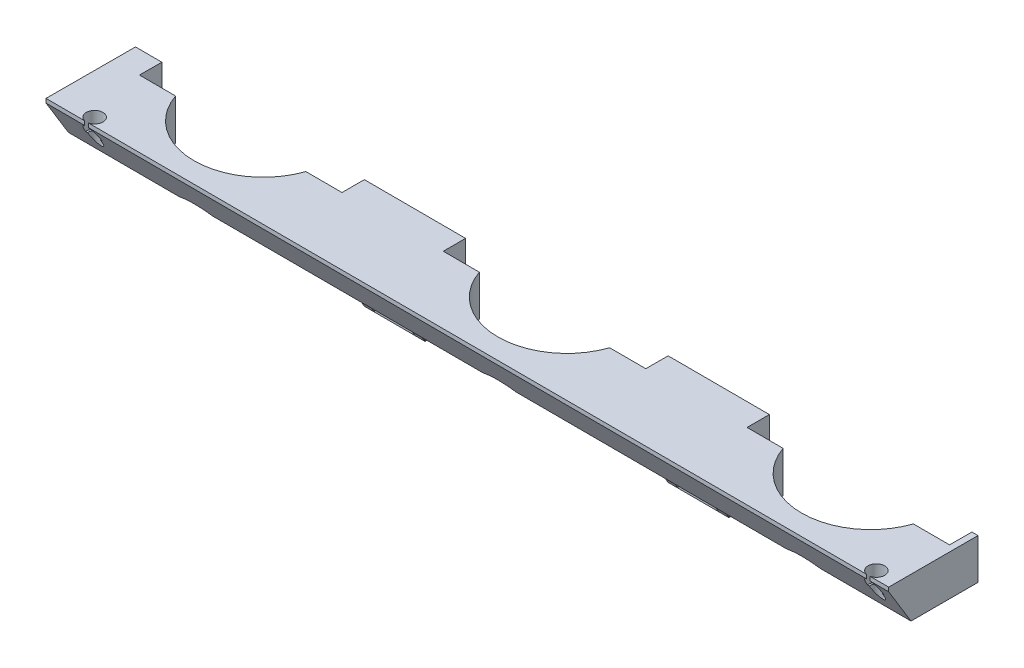
SolidWorks part; units mm, degrees
ref_plane "Płaszczyzna przednia" through (0, 0, 0) normal (0, 0, 1) x (1, 0, 0)
ref_plane "Płaszczyzna górna" through (0, 0, 0) normal (0, 1, 0) x (1, 0, 0)
ref_plane "Płaszczyzna prawa" through (0, 0, 0) normal (1, 0, 0) x (0, 0, -1)
sketch "Sketch2" plane through (0, 0, 0) normal (0, 1, 0) x (1, 0, 0)
  line L2 (-138.973, 39.1792) -> (-139.0228, 17.1793)
  line L3 (-139.0228, 17.1793) -> (73.9767, 16.6977)
  line L4 (74.027, 38.6976) -> (73.9767, 16.6977)
  line L5 (-107.4205, 62.3676) -> (-107.5199, 18.3936) construction
  line L7 (-132.4855, 33.6645) -> (-123.5712, 33.6443)
  line L9 (-132.4855, 33.6645) -> (-132.473, 39.1645)
  line L10 (-82.473, 39.0515) -> (-82.4855, 33.5515)
  line L11 (-138.973, 39.1792) -> (-132.473, 39.1645)
  line L12 (-57.4857, 33.4949) -> (-57.4732, 38.995)
  line L13 (-82.473, 39.0515) -> (-57.4732, 38.995)
  line L14 (-82.4855, 33.5515) -> (-91.3999, 33.5716)
  line L15 (-57.4857, 33.4949) -> (-48.5714, 33.4748)
  line L16 (-7.4857, 33.3819) -> (-16.4001, 33.402)
  line L17 (-7.4732, 38.8819) -> (-7.4857, 33.3819)
  line L18 (17.5141, 33.3253) -> (17.5266, 38.8254)
  line L19 (17.5141, 33.3253) -> (26.4284, 33.3052)
  line L20 (67.5141, 33.2123) -> (58.5997, 33.2325)
  line L21 (67.5266, 38.7123) -> (67.5141, 33.2123)
  line L22 (-7.4732, 38.8819) -> (17.5266, 38.8254)
  line L23 (67.5266, 38.7123) -> (74.027, 38.6976)
  arc A4 (-123.5712, 33.6443) -> (-91.3999, 33.5716) centre (-107.4731, 39.108) ccw
  arc A5 (-48.5714, 33.4748) -> (-16.4001, 33.402) centre (-32.4733, 38.9384) ccw
  arc A6 (26.4284, 33.3052) -> (58.5997, 33.2325) centre (42.5265, 38.7688) ccw
  point P4 (-104.1372, 39.0751)
  point P8 (-115.6371, 39.1103)
  point P12 (-95.973, 39.082)
  point P15 (-107.4702, 40.3806)
  dimension "D3" = 31.5
  dimension "D5" = 213
  dimension "D9" = 6.5
  dimension "D4" = 50.0001
  dimension "D14" = 34
  dimension "D11" = 17
  dimension "D1" = 213
  dimension "D2" = 22
  dimension "D6" = 360
  dimension "D7" = 13.5
  dimension "D8" = 213.0005
  dimension "D10" = 0
  dimension "D12" = 5.5
  dimension "D13" = 50
  dimension "D15" = 3
  dimension "D16" = 89.999
  dimension "D17" = 8.9143
extrude "Boss-Extrude3" add sketch "Sketch2" along normal blind 10
sketch "Sketch4" plane through (0.0879, 0, -38.8648) normal (0.0023, 0, -1) x (-1, 0, -0.0023)
  line L0 (62.5612, -12) -> (77.5612, -12)
  line L1 (62.5612, -12) -> (70.0612, -8.5) construction
  line L2 (57.5613, 0) -> (82.5611, 0) construction
  line L3 (77.5612, -12) -> (82.5611, 0)
  line L4 (62.5612, -12) -> (57.5613, 0)
  line L5 (77.5612, -12) -> (70.0612, -8.5) construction
  circle A0 centre (70.0612, -8.5) radius 1.5
  line M8 (57.5613, 0) -> (82.5611, 0)
  dimension "D3" = 3
  dimension "D1" = 15
  dimension "D2" = 12
  dimension "D4" = 3.5
extrude "Boss-Extrude4" add sketch "Sketch4" against normal blind 5 contours L4 L0 L3 A0 M8
ref_plane "Plane1" through (-77.561, 0, -0.1754) normal (1, 0, 0.0023) x (0.0023, 0, -1)
sketch "Sketch5" plane through (-77.561, 0, -0.1754) normal (1, 0, 0.0023) x (0.0023, 0, -1)
  line L0 (33.8649, -12) -> (26.8649, 0)
  line L5 (33.3649, 0) -> (33.8649, 0) construction
rib "Rib6" sketch "Sketch5" sketch "Sketch5" thickness 2.5 parameters "D1"=2.5
ref_plane "Plane3" through (-70.061, 0, -0.1584) normal (1, 0, 0.0023) x (0.0023, 0, -1)
mirror "Mirror2" about plane through (-70.061, 0, -0.1584) normal (1, 0, 0.0023) of "Rib6"
chamfer "Chamfer2" distance 1 angle 45 1 edges at (-71.4844, -8.5, -34.0266)
chamfer "Chamfer3" distance 5.5 distance2 9 1 edges at (-32.523, 0, -16.9385)
pattern_linear "LPattern4" count 2 spacing 75 along (1, 0, 0.0023) of "Boss-Extrude4", "Rib6", "Mirror2", "Chamfer2"
sketch "Sketch8" plane through (0, 10, 0) normal (0, 1, 0) x (1, 0, 0)
  line L0 (-138.973, 39.1792) -> (-139.0182, 19.1792)
  line L1 (-139.0182, 19.1792) -> (-129.0182, 19.1566)
  line L2 (-138.973, 39.1792) -> (-139.0228, 17.1793) construction
  circle A0 centre (-129.0182, 19.1566) radius 2.05
  dimension "D3" = 4.1
  dimension "D1" = 20
  dimension "D2" = 10
extrude "Cut-Extrude1" cut sketch "Sketch8" against normal blind 4
sketch "Sketch9" plane through (0, 6, 0) normal (0, 1, 0) x (1, 0, 0)
  circle A0 centre (-129.0182, 19.1566) radius 1.6
  circle A2 centre (-129.0182, 19.1566) radius 2.05 construction
  dimension "D1" = 3.2
extrude "Cut-Extrude2" cut sketch "Sketch9" against normal blind 5
ref_plane "Plane4" through (-32.5612, 0, -0.0736) normal (-1, 0, -0.0023) x (-0.0023, 0, 1)
mirror "Mirror4" about plane through (-32.5612, 0, -0.0736) normal (-1, 0, -0.0023) of "Cut-Extrude2", "Cut-Extrude1"
sketch "Szkic1" plane through (0, 10, 0) normal (0, 1, 0) x (1, 0, 0)
  line L1 (77.5784, 15.1188) -> (69.0264, 15.1188)
  line L2 (77.5784, 15.1188) -> (77.5784, 38.7089)
  line L3 (77.5784, 38.7089) -> (69.0264, 38.7089)
  line L4 (69.0264, 15.1188) -> (69.0264, 38.7089)
  line L5 (74.027, 38.6976) -> (67.5266, 38.7123) construction
  point P4 (77.5784, 38.705)
  point P5 (69.0264, 38.7089)
  point P8 (74.2734, 13.2428)
  point P9 (73.9731, 15.1188)
extrude "Wytnij-wyciągnięcie3" cut sketch "Szkic1" against normal blind 30.5
